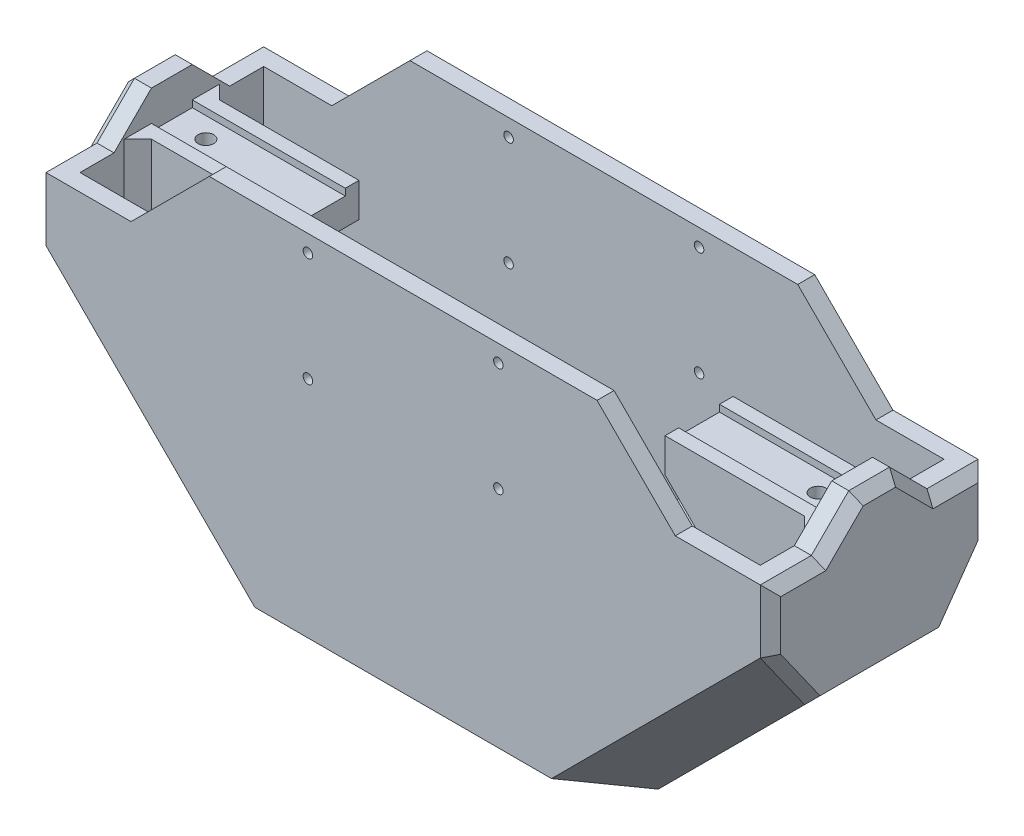
SolidWorks part; units mm, degrees
ref_plane "Front Plane" through (0, 0, 0) normal (0, 0, 1) x (1, 0, 0)
ref_plane "Top Plane" through (0, 0, 0) normal (0, 1, 0) x (1, 0, 0)
ref_plane "Right Plane" through (0, 0, 0) normal (1, 0, 0) x (0, 0, -1)
sketch "Sketch1" plane through (0, 0, 0) normal (0, 1, 0) x (1, 0, 0)
  line L1 (-100, -27) -> (100, -27)
  line L2 (-100, -27) -> (-100, 27)
  line L3 (-100, 27) -> (100, 27)
  line L4 (100, -27) -> (100, 27)
  line L5 (-100, -27) -> (100, 27) construction
  line L6 (-100, 27) -> (100, -27) construction
  point P0 (0, 0)
  dimension "D1" = 200
  dimension "D2" = 54
extrude "Boss-Extrude1" add sketch "Sketch1" along normal blind 75
shell "Shell1" thickness 5
sketch "Sketch2" plane through (105, 0, 0) normal (1, 0, 0) x (0, 0, -1)
  line L0 (-17, 75) -> (-6, 86)
  line L1 (-32, 75) -> (32, 75) construction
  line L2 (-6, 86) -> (6, 86)
  line L3 (6, 86) -> (17, 75)
  line L4 (17, 75) -> (-17, 75)
  line L5 (0, 86) -> (0, 75) construction
  dimension "D1" = 11
  dimension "D2" = 45
  dimension "D3" = 45
  dimension "D4" = 12
extrude "Boss-Extrude2" add sketch "Sketch2" against normal blind 5
sketch "Sketch4" plane through (0, 0, -32) normal (0, 0, -1) x (-1, 0, 0)
  line L0 (-80, 75) -> (-57, 98)
  line L1 (-105, 75) -> (105, 75) construction
  line L2 (-57, 98) -> (57, 98)
  line L3 (57, 98) -> (80, 75)
  line L4 (80, 75) -> (-80, 75)
  line L5 (0, 98) -> (0, 75) construction
  line L6 (-105, 75) -> (-105, -5) construction
  dimension "D1" = 23
  dimension "D2" = 25
  dimension "D3" = 45
extrude "Boss-Extrude3" add sketch "Sketch4" against normal blind 5
sketch "Sketch3" plane through (0, 0, -32) normal (0, 0, -1) x (-1, 0, 0)
  line L1 (-28, 61) -> (28, 61) construction
  line L2 (-28, 61) -> (-28, 93) construction
  line L3 (-28, 93) -> (28, 93) construction
  line L4 (28, 61) -> (28, 93) construction
  line L5 (-28, 61) -> (28, 93) construction
  line L6 (-28, 93) -> (28, 61) construction
  line L7 (57, 98) -> (-57, 98) construction
  circle A0 centre (-28, 93) radius 1.4
  circle A1 centre (-28, 61) radius 1.4
  circle A2 centre (28, 93) radius 1.4
  circle A3 centre (28, 61) radius 1.4
  point P0 (0, 77)
  dimension "D1" = 2.8
  dimension "D2" = 56
  dimension "D3" = 32
  dimension "D4" = 5
extrude "Cut-Extrude1" cut sketch "Sketch3" against normal blind 6
mirror "Mirror4" about plane through (0, 0, 0) normal (0, 0, 1) of "Boss-Extrude3", "Cut-Extrude1"
mirror "Mirror5" about plane through (0, 0, 0) normal (1, 0, 0) of "Boss-Extrude2"
sketch "Sketch5" plane through (0, 0, 0) normal (0, 0, 1) x (1, 0, 0)
  line L0 (-100, 75) -> (-55, 75)
  line L1 (-55, 75) -> (-55, 67)
  line L2 (-55, 67) -> (-100, 22)
  line L4 (-100, 22) -> (-100, 75)
  line L5 (-100, 86) -> (-100, 75) construction
  line L6 (-105, 75) -> (-80, 75) construction
  dimension "D1" = 45
  dimension "D2" = 8
  dimension "D3" = 45
extrude "Boss-Extrude4" add sketch "Sketch5" along normal mid plane 20
sketch "Sketch9" plane through (0, 75, 0) normal (0, 1, 0) x (1, 0, 0)
  line L4 (-55, 10) -> (-100, 10)
  line L5 (-100, 10) -> (-100, -10)
  line L6 (-100, -10) -> (-55, -10)
  line L7 (-55, -10) -> (-55, 10)
  line L8 (-55, 10) -> (-100, 10)
  line L10 (-100, -10) -> (-55, -10)
  line L11 (-55, -10) -> (-55, 10)
  line L13 (-100, 10) -> (-100, -10)
  dimension "D1" = 0
extrude "Boss-Extrude6" add sketch "Sketch9" along normal blind 2
sketch "Sketch10" plane through (-100, 0, 0) normal (1, 0, 0) x (0, 0, -1)
  line L0 (-10, 77) -> (10, 77) construction
  line L1 (-6, 77) -> (6, 77)
  line L2 (-6, 77) -> (-6, 75)
  line L3 (-6, 75) -> (6, 75)
  line L4 (6, 77) -> (6, 75)
  line L5 (-6, 77) -> (6, 75) construction
  line L6 (-6, 75) -> (6, 77) construction
  point P0 (0, 76)
  dimension "D1" = 2
  dimension "D2" = 12
extrude "Cut-Extrude2" cut sketch "Sketch10" along normal up to next
sketch "Sketch11" plane through (0, 75, 0) normal (0, 1, 0) x (1, 0, 0)
  line L1 (-100, 6) -> (-100, -6) construction
  circle A0 centre (-90, 0) radius 2.3
  dimension "D1" = 4.6
  dimension "D2" = 10
extrude "Cut-Extrude3" cut sketch "Sketch11" against normal blind 6
mirror "Mirror24" about plane through (0, 0, 0) normal (1, 0, 0) of "Cut-Extrude2", "Boss-Extrude4", "Boss-Extrude6", "Cut-Extrude3"
sketch "Sketch13" plane through (0, 0, 0) normal (0, 0, 1) x (1, 0, 0)
  line L1 (-21, 16.2) -> (41, 16.2)
  line L2 (-21, 16.2) -> (-21, 31.2)
  line L3 (-21, 31.2) -> (41, 31.2)
  line L4 (41, 16.2) -> (41, 31.2)
  line L5 (-21, 16.2) -> (41, 31.2) construction
  line L6 (-21, 31.2) -> (41, 16.2) construction
  line L11 (-10.5, 31.2) -> (-10.5, 16.2)
  line L12 (30.5, 31.2) -> (30.5, 16.2)
  line L13 (-100, 0) -> (100, 0) construction
  point P0 (10, 23.7)
  dimension "D1" = 62
  dimension "D2" = 15
  dimension "D3" = 31.2
  dimension "D4" = 10
  dimension "D5" = 41
  dimension "D6" = 10.5
extrude "Boss-Extrude8" add sketch "Sketch13" along normal mid plane 54 contours L3 L12 L1 L4 | L11 L3 L2 L1
sketch "Sketch14" plane through (0, 31.2, 0) normal (0, 1, 0) x (1, 0, 0)
  line L0 (-10.5, -27) -> (-10.5, 27) construction
  line L1 (-10.5, -9.6) -> (-15.5, -9.6)
  line L2 (-10.5, -9.6) -> (-10.5, 9.6)
  line L3 (-10.5, 9.6) -> (-15.5, 9.6)
  line L4 (-17.5, -7.6) -> (-17.5, 7.6)
  line L5 (-17.5, 9.6) -> (-10.5, -9.6) construction
  line L10 (-10.5, 27) -> (-21, 27)
  line L11 (-21, 27) -> (-21, -27)
  line L12 (-21, -27) -> (-10.5, -27)
  line L13 (-10.5, -27) -> (-10.5, 27)
  line L14 (-10.5, 27) -> (-21, 27)
  line L15 (-21, 27) -> (-21, -27)
  line L16 (-21, -27) -> (-10.5, -27)
  line L17 (-10.5, -27) -> (-10.5, 27)
  arc A0 (-15.5, -9.6) -> (-17.5, -7.6) centre (-15.5, -7.6) cw
  arc A1 (-15.5, 9.6) -> (-17.5, 7.6) centre (-15.5, 7.6) ccw
  point P6 (-14, 0)
  point P11 (-17.5, -9.6)
  dimension "D3" = 2
  dimension "D1" = 19.2
  dimension "D2" = 7
  dimension "D4" = 0
extrude "Boss-Extrude9" add sketch "Sketch14" along normal blind 3.2
sketch "Sketch15" plane through (0, 31.2, 0) normal (0, 1, 0) x (1, 0, 0)
  line L0 (-14.8, 5) -> (-14.8, -5) construction
  line L1 (-17.5, -7.6) -> (-17.5, 7.6) construction
  circle A0 centre (-14.8, 5) radius 1.4
  circle A1 centre (-14.8, -5) radius 1.4
  point P4 (-14.8, 0)
  dimension "D1" = 10
  dimension "D2" = 2.8
  dimension "D3" = 2.7
extrude "Cut-Extrude4" cut sketch "Sketch15" against normal up to next
chamfer "Chamfer8" distance 0.5 angle 45 2 edges at (-16.2, 31.2, 5) (-16.2, 31.2, -5)
ref_plane "Plane1" through (10, 0, 0) normal (1, 0, 0) x (0, 0, -1)
mirror "Mirror6" about plane through (10, 0, 0) normal (1, 0, 0) of "Chamfer8", "Cut-Extrude4", "Boss-Extrude9"
chamfer "Chamfer3" distance 40 angle 45 2 edges at (100, 0, 0) (-100, 0, 0)
chamfer "Chamfer5" distance 43 angle 45 2 edges at (-105, -5, 0) (105, -5, 0)
chamfer "Chamfer9" distance 5 angle 45 4 edges at (35.75, 16.2, -27) (-15.75, 16.2, -27) (-15.75, 16.2, 27) (35.75, 16.2, 27)
chamfer "Chamfer10" distance 2 angle 45 8 edges at (41, 22.8, -27) (30.5, 22.8, -27) (-10.5, 22.8, -27) (-21, 22.8, -27) (-21, 22.8, 27) (-10.5, 22.8, 27) (30.5, 22.8, 27) (41, 22.8, 27)
chamfer "Chamfer11" distance 10 angle 45 4 edges at (80, 20, 27) (80, 20, -27) (-80, 20, -27) (-80, 20, 27)
chamfer "Chamfer12" distance 13 angle 45 4 edges at (-83.5, 16.5, -32) (83.5, 16.5, -32) (-83.5, 16.5, 32) (83.5, 16.5, 32)
chamfer "Chamfer13" distance 4 angle 45 4 edges at (-100, 58.5, -10) (-100, 58.5, 10) (100, 58.5, 10) (100, 58.5, -10)
sketch "Sketch16" plane through (105, 0, 0) normal (1, 0, 0) x (0, 0, -1)
  line L10 (-19, 38) -> (19, 38)
  line L11 (19, 38) -> (32, 56.3848)
  line L12 (32, 56.3848) -> (32, 75)
  line L13 (32, 75) -> (17, 75)
  line L14 (17, 75) -> (6, 86)
  line L15 (6, 86) -> (-6, 86)
  line L16 (-6, 86) -> (-17, 75)
  line L17 (-17, 75) -> (-32, 75)
  line L18 (-32, 75) -> (-32, 56.3848)
  line L19 (-32, 56.3848) -> (-19, 38)
  line L20 (-19, 38) -> (19, 38)
  line L21 (19, 38) -> (32, 56.3848)
  line L22 (32, 56.3848) -> (32, 75)
  line L23 (32, 75) -> (17, 75)
  line L24 (17, 75) -> (6, 86)
  line L25 (6, 86) -> (-6, 86)
  line L26 (-6, 86) -> (-17, 75)
  line L27 (-17, 75) -> (-32, 75)
  line L28 (-32, 75) -> (-32, 56.3848)
  line L29 (-32, 56.3848) -> (-19, 38)
  dimension "D1" = 0
extrude "Boss-Extrude10" add sketch "Sketch16" along normal blind 3
chamfer "Chamfer14" distance 3 angle 45 10 edges at (108, 65.6924, 32) (108, 75, 24.5) (108, 80.5, 11.5) (108, 86, 0) (108, 80.5, -11.5) (108, 75, -24.5) (108, 65.6924, -32) (108, 47.1924, -25.5) (108, 38, 0) (108, 47.1924, 25.5)
mirror "Mirror28" about plane through (0, 0, 0) normal (1, 0, 0) of "Chamfer14", "Boss-Extrude10"
